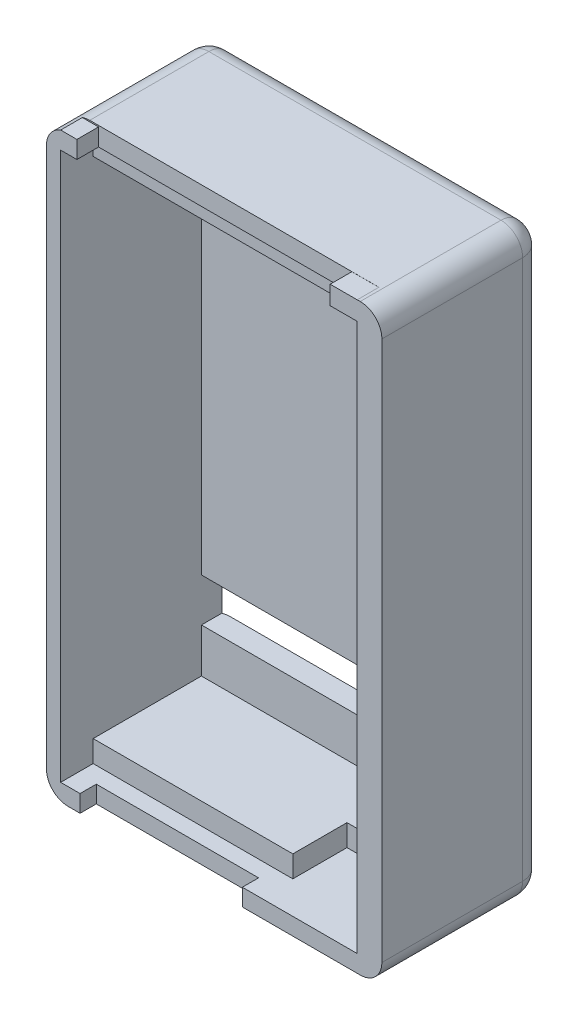
SolidWorks part; units mm, degrees
ref_plane "Front Plane" through (0, 0, 0) normal (0, 0, 1) x (1, 0, 0)
ref_plane "Top Plane" through (0, 0, 0) normal (0, 1, 0) x (1, 0, 0)
ref_plane "Right Plane" through (0, 0, 0) normal (1, 0, 0) x (0, 0, -1)
sketch "草图3" plane through (0, 0, 0) normal (0, 0, 1) x (1, 0, 0)
  line L6 (37.1016, -24.8877) -> (68.0762, -24.8877)
  line L7 (68.0762, -24.8877) -> (68.0762, -78.7564)
  line L10 (68.0762, -78.7564) -> (37.1016, -78.7564)
  line L11 (37.1016, -78.7564) -> (37.1016, -24.8877)
  line L12 (40.0889, -26.8877) -> (65.0889, -26.8877) construction
  line L13 (66.0762, -27.875) -> (66.0762, -75.875) construction
  line L14 (39.1016, -72.8424) -> (39.1016, -48.9006) construction
  line L16 (39.1016, -29.6037) -> (39.1016, -27.875) construction
  line L17 (39.1016, -48.9006) -> (39.1016, -29.6496) construction
  line L18 (39.1016, -75.875) -> (39.1016, -72.8424) construction
  line L19 (58.7612, -76.8631) -> (40.0889, -76.8624) construction
  line L20 (58.7612, -75.262) -> (58.7612, -76.8631) construction
  line L21 (62.9649, -75.2493) -> (58.7739, -75.2493) construction
  line L22 (62.9776, -76.8751) -> (62.9776, -75.262) construction
  line L23 (65.0889, -76.8624) -> (62.9776, -76.9001) construction
  line L24 (39.1016, -29.6037) -> (39.1016, -27.875)
  line L25 (39.1016, -48.9006) -> (39.1016, -29.6496)
  line L26 (39.1016, -72.8424) -> (39.1016, -48.9006)
  line L27 (39.1016, -75.875) -> (39.1016, -72.8424)
  line L28 (58.7612, -76.8631) -> (40.0889, -76.8624)
  line L29 (58.7612, -75.262) -> (58.7612, -76.8631)
  line L30 (62.9649, -75.2493) -> (58.7739, -75.2493)
  line L31 (62.9776, -76.8751) -> (62.9776, -75.262)
  line L32 (65.0889, -76.8624) -> (62.9776, -76.9001)
  line L33 (66.0762, -27.875) -> (66.0762, -75.875)
  line L34 (40.0889, -26.8877) -> (65.0889, -26.8877)
  arc A0 (39.1016, -75.875) -> (40.0889, -76.8624) centre (40.0889, -75.875) ccw construction
  arc A1 (65.0889, -76.8624) -> (66.0762, -75.875) centre (65.0889, -75.875) ccw construction
  arc A2 (66.0762, -27.875) -> (65.0889, -26.8877) centre (65.0889, -27.875) ccw construction
  arc A3 (40.0889, -26.8877) -> (39.1016, -27.875) centre (40.0889, -27.875) ccw construction
  arc A4 (39.1016, -75.875) -> (40.0889, -76.8624) centre (40.0889, -75.875) ccw
  arc A5 (65.0889, -76.8624) -> (66.0762, -75.875) centre (65.0889, -75.875) ccw
  arc A6 (66.0762, -27.875) -> (65.0889, -26.8877) centre (65.0889, -27.875) ccw
  arc A7 (40.0889, -26.8877) -> (39.1016, -27.875) centre (40.0889, -27.875) ccw
  dimension "D1" = 2
  dimension "D2" = 2
  dimension "D3" = 2
extrude "凸台-拉伸1" add sketch "草图3" along normal blind 15 contours L11 L10 L7 L6 region at (52.5889, -51.822, 0)
sketch "草图5" plane through (0, 0, 15) normal (0, 0, 1) x (1, 0, 0)
  line L1 (38.4139, -26.6161) -> (65.7955, -26.6161)
  line L2 (65.7955, -26.6161) -> (65.7955, -77.1753)
  line L3 (65.7955, -77.1753) -> (38.4139, -77.1753)
  line L4 (38.4139, -77.1753) -> (38.4139, -26.6161)
extrude "切除-拉伸1" cut sketch "草图5" against normal blind 13
sketch "草图6" plane through (0, 0, 2) normal (0, 0, 1) x (1, 0, 0)
  line L0 (38.4139, -26.6161) -> (38.4139, -77.1753) construction
  line L1 (38.4139, -26.6161) -> (65.7955, -26.6161)
  line L2 (38.4139, -26.6161) -> (38.4139, -28.6161)
  line L3 (38.4139, -28.6161) -> (65.7955, -28.6161)
  line L4 (65.7955, -26.6161) -> (65.7955, -28.6161)
  line L5 (65.7955, -26.6161) -> (38.4139, -26.6161) construction
  line L6 (65.7955, -77.1753) -> (65.7955, -26.6161) construction
  line L7 (65.7955, -77.1753) -> (65.7955, -26.6161) construction
  line L8 (38.4139, -77.1753) -> (65.7955, -77.1753)
  line L9 (38.4139, -77.1753) -> (38.4139, -75.1753)
  line L10 (38.4139, -75.1753) -> (65.7955, -75.1753)
  line L11 (65.7955, -77.1753) -> (65.7955, -75.1753)
extrude "凸台-拉伸2" add sketch "草图6" along normal blind 10
sketch "草图9" plane through (0, 0, 15) normal (0, 0, 1) x (1, 0, 0)
  line L0 (37.1016, -24.8877) -> (68.0762, -24.8877) construction
  line L1 (38.4139, -26.6161) -> (65.8048, -26.6161)
  line L2 (38.4139, -26.6161) -> (38.4139, -24.8877)
  line L3 (38.4139, -24.8877) -> (65.8048, -24.8877)
  line L4 (65.8048, -26.6161) -> (65.8048, -24.8877)
extrude "切除-拉伸3" cut sketch "草图9" against normal blind 2
fillet "圆角1" radius 2 4 edges at (68.0762, -78.7564, 7.5) (37.1016, -78.7564, 7.5) (37.1016, -24.8877, 7.5) (68.0762, -24.8877, 7.5)
sketch "草图11" plane through (0, 0, 2) normal (0, 0, 1) x (1, 0, 0)
  line L0 (38.4139, -28.6161) -> (38.4139, -75.1753) construction
  line L1 (38.4139, -32.8271) -> (65.7955, -32.8271)
  line L2 (38.4139, -32.8271) -> (38.4139, -36.8271)
  line L3 (38.4139, -36.8271) -> (65.7955, -36.8271)
  line L4 (65.7955, -32.8271) -> (65.7955, -36.8271)
  line L5 (65.7955, -77.1753) -> (65.7955, -26.6161) construction
  line L7 (38.4139, -67.0903) -> (65.7955, -67.0903)
  line L8 (38.4139, -67.0903) -> (38.4139, -71.0903)
  line L9 (38.4139, -71.0903) -> (65.7955, -71.0903)
  line L10 (65.7955, -67.0903) -> (65.7955, -71.0903)
extrude "切除-拉伸4" cut sketch "草图11" against normal blind 10
sketch "草图12" plane through (0, 0, 12) normal (0, 0, 1) x (1, 0, 0)
  line L0 (65.7955, -75.1753) -> (38.4139, -75.1753) construction
  line L1 (56.855, -75.1753) -> (62.9048, -75.1753)
  line L2 (56.855, -75.1753) -> (56.855, -77.1753)
  line L3 (56.855, -77.1753) -> (62.9048, -77.1753)
  line L4 (62.9048, -75.1753) -> (62.9048, -77.1753)
  line L5 (38.4139, -77.1753) -> (65.7955, -77.1753) construction
extrude "切除-拉伸5" cut sketch "草图12" against normal blind 5
sketch "草图14" plane through (0, 0, 13) normal (0, 0, 1) x (1, 0, 0)
  line L0 (38.4139, -26.6161) -> (65.7955, -26.6161) construction
  line L1 (38.4139, -25.0096) -> (39.9139, -25.0096)
  line L2 (38.4139, -25.0096) -> (38.4139, -26.6161)
  line L3 (38.4139, -26.6161) -> (39.9139, -26.6161)
  line L4 (39.9139, -25.0096) -> (39.9139, -26.6161)
  line L6 (65.8048, -24.8943) -> (63.3048, -24.8943)
  line L7 (65.8048, -24.8943) -> (65.8048, -26.6161)
  line L8 (65.8048, -26.6161) -> (63.3048, -26.6161)
  line L9 (63.3048, -24.8943) -> (63.3048, -26.6161)
extrude "凸台-拉伸3" add sketch "草图14" along normal up to surface (2 mm away) contours L2 L1 L4 L3 | L7 L6 L9 L8 up to face at (55.5197, -49.7982, 15)
sketch "草图17" plane through (0, 0, 15) normal (0, 0, 1) x (1, 0, 0)
  line L1 (40.2057, -77.1564) -> (55.1901, -77.1564)
  line L2 (40.2057, -77.1564) -> (40.2057, -78.7564)
  line L3 (40.2057, -78.7564) -> (55.1901, -78.7564)
  line L4 (55.1901, -77.1564) -> (55.1901, -78.7564)
extrude "切除-拉伸8" cut sketch "草图17" against normal blind 1.5
fillet "圆角2" radius 2 8 edges at (37.6874, -25.4734, 0) (37.1016, -51.822, 0) (37.6874, -78.1706, 0) (52.5889, -78.7564, 0) (67.4904, -78.1706, 0) (68.0762, -51.822, 0) (67.4904, -25.4734, 0) (52.5889, -24.8877, 0)
